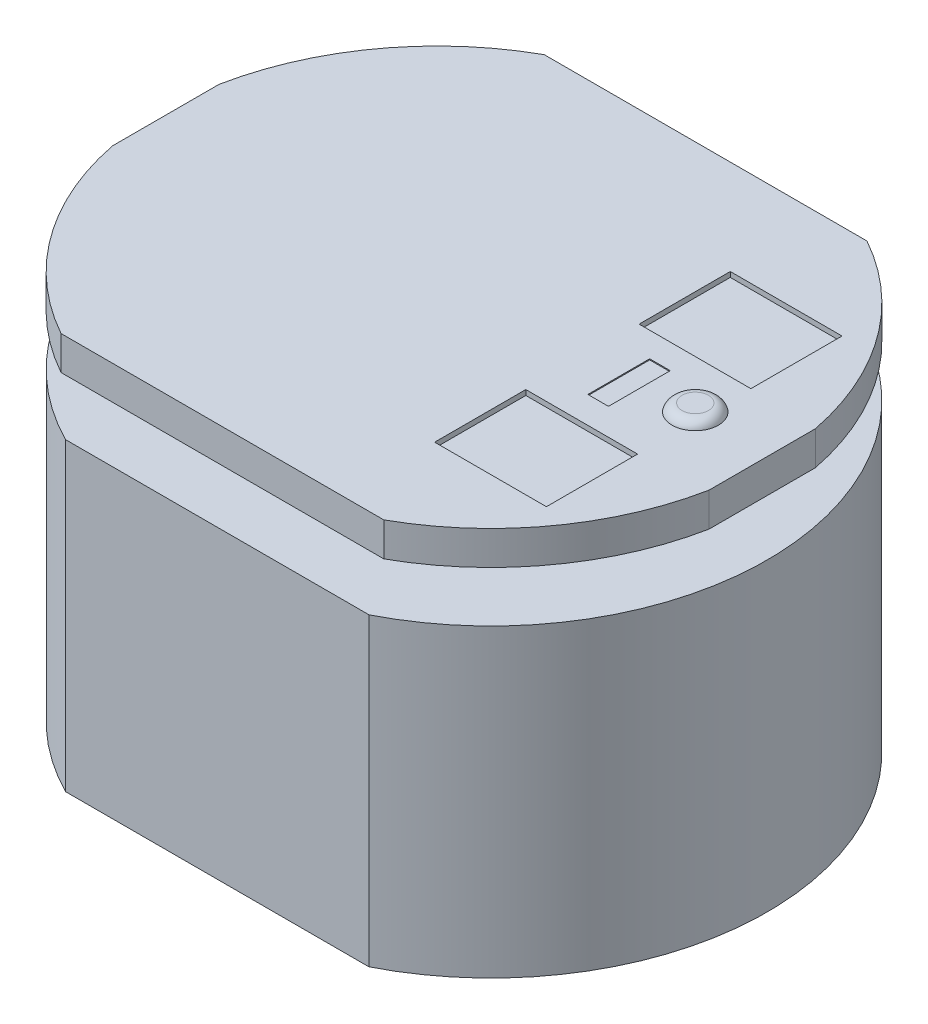
SolidWorks part; units mm, degrees
ref_plane "Plano frontal" through (0, 0, 0) normal (0, 0, 1) x (1, 0, 0)
ref_plane "Plano superior" through (0, 0, 0) normal (0, 1, 0) x (1, 0, 0)
ref_plane "Plano direito" through (0, 0, 0) normal (1, 0, 0) x (0, 0, -1)
sketch "Esboço1" plane through (0, 0, 0) normal (0, 1, 0) x (1, 0, 0)
  line L1 (294.5, -239.5) -> (-294.5, -239.5)
  line L2 (294.5, -239.5) -> (294.5, 239.5)
  line L3 (294.5, 239.5) -> (-294.5, 239.5)
  line L4 (-294.5, -239.5) -> (-294.5, 239.5)
  line L5 (294.5, -239.5) -> (-294.5, 239.5) construction
  line L6 (294.5, 239.5) -> (-294.5, -239.5) construction
  point P0 (0, 0)
  dimension "D1" = 589
  dimension "D2" = 479
extrude "Ressalto-extrusão1" add sketch "Esboço1" along normal blind 296
sketch "Esboço2" plane through (0, 296, 0) normal (0, 1, 0) x (1, 0, 0)
  line L1 (-110, 90) -> (110, 90)
  line L2 (-110, 90) -> (-110, -90)
  line L3 (-110, -90) -> (110, -90)
  line L4 (110, 90) -> (110, -90)
  line L5 (-110, 90) -> (110, -90) construction
  line L6 (-110, -90) -> (110, 90) construction
  point P0 (0, 0)
  dimension "D1" = 220
  dimension "D2" = 180
extrude "Ressalto-extrusão2" add sketch "Esboço2" along normal blind 49.2
sketch "Esboço3" plane through (0, 345.2, 0) normal (0, 1, 0) x (1, 0, 0)
  line L1 (-289.5, 234.5) -> (289.5, 234.5)
  line L2 (-289.5, 234.5) -> (-289.5, -234.5)
  line L3 (-289.5, -234.5) -> (289.5, -234.5)
  line L4 (289.5, 234.5) -> (289.5, -234.5)
  line L5 (-289.5, 234.5) -> (289.5, -234.5) construction
  line L6 (-289.5, -234.5) -> (289.5, 234.5) construction
  point P0 (0, 0)
  dimension "D1" = 579
  dimension "D2" = 469
extrude "Ressalto-extrusão3" add sketch "Esboço3" along normal blind 32.8
sketch "Esboço4" plane through (0, 378, 0) normal (0, 1, 0) x (1, 0, 0)
  line L0 (0, 239.5) -> (0, -239.5) construction
  line L1 (294.5, 239.5) -> (-294.5, 239.5) construction
  line L3 (147.25, 239.5) -> (-147.25, 239.5) construction
  line L4 (-294.5, -239.5) -> (294.5, -239.5) construction
  line L5 (-147.25, -239.5) -> (147.25, -239.5) construction
  line L6 (-294.5, 239.5) -> (-294.5, -239.5) construction
  line L8 (-147.25, 239.5) -> (-294.5, 239.5)
  line L9 (-294.5, 239.5) -> (-294.5, -239.5)
  line L10 (-294.5, -239.5) -> (-147.25, -239.5)
  line L11 (147.25, -239.5) -> (294.5, -239.5)
  line L12 (294.5, -239.5) -> (294.5, 239.5)
  line L13 (294.5, 239.5) -> (147.25, 239.5)
  arc A0 (-147.25, 239.5) -> (-147.25, -239.5) centre (-26.1034, 0) ccw
  arc A1 (147.25, 239.5) -> (147.25, -239.5) centre (26.1034, 0) cw
  arc A2 (147.25, 239.5) -> (147.25, -239.5) centre (26.1034, 0) cw
  point P14 (-294.5, 0)
  line M3 (289.5, -234.5) -> (289.5, 234.5)
  line M4 (289.5, 234.5) -> (-289.5, 234.5)
  line M5 (-289.5, 234.5) -> (-289.5, -234.5)
  line M6 (-289.5, -234.5) -> (289.5, -234.5)
  dimension "D1" = 147.25
extrude "Corte-extrusão1" cut sketch "Esboço4" against normal up to surface (378 mm away) contours A0 M5 M6 | A0 M4 M5 | A1 M4 M3 | A1 M3 M6 | L13 A1 L12 M4 M3 | L12 A1 L11 M3 M6 | A0 L9 L10 M6 M5 | A0 L8 L9 M5 M4 region at (-152.1145, 378, -237.2951) region at (-251.6024, 378, -184.7117) region at (-293.5269, 378, 25.9306) region at (251.6024, 378, -184.7117) region at (152.1145, 378, -237.2951) region at (-251.6024, 378, 184.7117) region at (291.6885, 378, 119.75) region at (251.6024, 378, 184.7117) up to face at (0, 0, 0)
sketch "Esboço5" plane through (0, 378, 0) normal (0, 1, 0) x (1, 0, 0)
  line L0 (-156.6656, -234.5) -> (156.6656, -234.5) construction
  line L1 (116, -144.5) -> (224.5, -144.5)
  line L2 (116, -144.5) -> (116, -56)
  line L3 (116, -56) -> (224.5, -56)
  line L4 (224.5, -144.5) -> (224.5, -56)
  line L5 (116, -144.5) -> (224.5, -56) construction
  line L6 (116, -56) -> (224.5, -144.5) construction
  line L7 (116, 54) -> (224.5, 54)
  line L8 (116, 54) -> (116, 142.5)
  line L9 (116, 142.5) -> (224.5, 142.5)
  line L10 (224.5, 54) -> (224.5, 142.5)
  line L11 (116, 54) -> (224.5, 142.5) construction
  line L12 (116, 142.5) -> (224.5, 54) construction
  arc A0 (147.25, -239.5) -> (147.25, 239.5) centre (26.1034, 0) ccw construction
  point P0 (170.25, -100.25)
  point P5 (170.25, 98.25)
  point P16 (294.5, 0)
  dimension "D1" = 88.5
  dimension "D2" = 108.5
  dimension "D3" = 90
  dimension "D4" = 110
  dimension "D5" = 70
extrude "Corte-extrusão2" cut sketch "Esboço5" against normal blind 5
sketch "Esboço6" plane through (0, 378, 0) normal (0, 1, 0) x (1, 0, 0)
  line L1 (224.5, -144.5) -> (224.5, -56) construction
  circle A0 centre (224.5, 0) radius 10
  point P7 (224.5, -100.25)
  dimension "D1" = 20
extrude "Ressalto-extrusão4" add sketch "Esboço6" along normal blind 7.5
sketch "Esboço7" plane through (0, 385.5, 0) normal (0, 1, 0) x (1, 0, 0)
  circle A0 centre (224.5, 0) radius 22.5
  dimension "D1" = 45
extrude "Ressalto-extrusão5" add sketch "Esboço7" along normal blind 7.5
fillet "Filete1" radius 10 1 edges at (224.5, 393, 22.5)
sketch "Esboço8" plane through (0, 378, 0) normal (0, 1, 0) x (1, 0, 0)
  line L1 (170.25, 30) -> (150.25, 30)
  line L2 (170.25, 30) -> (170.25, -30)
  line L3 (170.25, -30) -> (150.25, -30)
  line L4 (150.25, 30) -> (150.25, -30)
  line L5 (170.25, 30) -> (150.25, -30) construction
  line L6 (170.25, -30) -> (150.25, 30) construction
  line L7 (116, 54) -> (224.5, 54) construction
  line L8 (116, 54) -> (224.5, 54) construction
  point P0 (160.25, 0)
  point P9 (170.25, 54)
  dimension "D1" = 20
  dimension "D2" = 60
  dimension "D3" = 10
  dimension "D4" = 24
extrude "Corte-extrusão3" cut sketch "Esboço8" against normal blind 1
